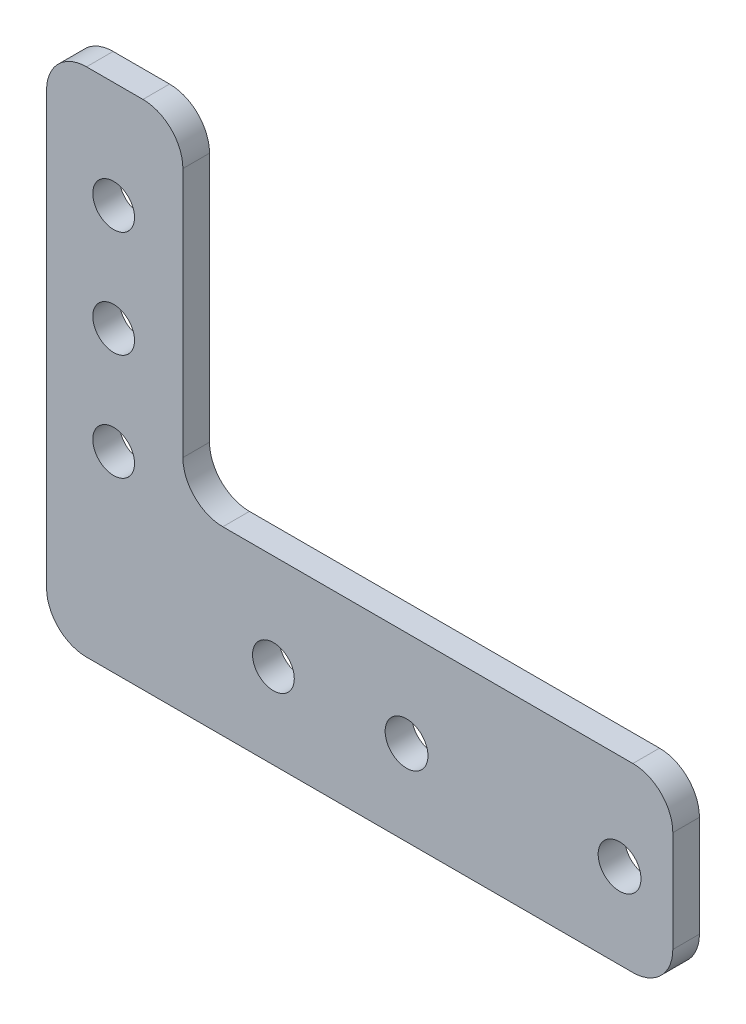
SolidWorks part; units mm, degrees
material "6061-T6 (SS)"
ref_plane "Front Plane" through (0, 0, 0) normal (0, 0, 1) x (1, 0, 0)
ref_plane "Top Plane" through (0, 0, 0) normal (0, 1, 0) x (1, 0, 0)
ref_plane "Right Plane" through (0, 0, 0) normal (1, 0, 0) x (0, 0, -1)
sketch "Sketch1" plane through (0, 0, 0) normal (0, 0, 1) x (1, 0, 0)
  line L1 (-41.275, -31.75) -> (41.275, -31.75)
  line L2 (-41.275, -31.75) -> (-41.275, 31.75)
  line L3 (-41.275, 31.75) -> (41.275, 31.75)
  line L4 (41.275, -31.75) -> (41.275, 31.75)
  line L5 (-41.275, -31.75) -> (41.275, 31.75) construction
  line L6 (-41.275, 31.75) -> (41.275, -31.75) construction
  line L7 (41.275, 31.75) -> (-17.145, 31.75)
  line L8 (41.275, 31.75) -> (41.275, -7.62)
  line L9 (41.275, -7.62) -> (-17.145, -7.62)
  line L10 (-17.145, 31.75) -> (-17.145, -7.62)
  line L11 (-41.275, -31.75) -> (-33.401, -31.75)
  line L12 (-41.275, -31.75) -> (-41.275, 31.75)
  line L13 (-41.275, 31.75) -> (-33.401, 31.75)
  line L14 (-33.401, -31.75) -> (-33.401, 31.75)
  line L15 (-33.401, -31.75) -> (41.275, -31.75)
  line L16 (-33.401, -31.75) -> (-33.401, -29.21)
  line L17 (-33.401, -29.21) -> (41.275, -29.21)
  line L18 (41.275, -31.75) -> (41.275, -29.21)
  circle A0 centre (-25.4, -19.05) radius 2.4892
  circle A1 centre (-25.4, -6.35) radius 2.4892
  circle A2 centre (-25.4, 6.35) radius 2.4892
  circle A3 centre (-25.4, 19.05) radius 2.4892
  circle A4 centre (-6.35, -19.05) radius 2.4892
  circle A5 centre (9.525, -19.05) radius 2.5527
  circle A7 centre (34.925, -19.05) radius 2.5527
  point P0 (0, 0)
  point P24 (0, 0)
  dimension "D7" = 4.9784
  dimension "D18" = 5.1054
  dimension "D1" = 82.55
  dimension "D2" = 63.5
  dimension "D3" = 24.13
  dimension "D4" = 24.13
  dimension "D5" = 7.874
  dimension "D6" = 63.5
  dimension "D8" = 15.875
  dimension "D9" = 12.7
  dimension "D10" = 12.7
  dimension "D11" = 12.7
  dimension "D12" = 12.7
  dimension "D13" = 25.4
  dimension "D14" = 27.051
  dimension "D15" = 15.875
  dimension "D16" = 2.54
extrude "Boss-Extrude1" add sketch "Sketch1" along normal blind 3.175 contours L14 L17 L4 L9 L10 L3 A5 A4 A3 A2 A1 A0 | A0 region at (-4.0851, -9.8474, 0) region at (-25.4, -19.05, 0)
fillet "Fillet1" radius 4.7625 6 edges at (-33.401, 31.75, 1.5875) (-17.145, 31.75, 1.5875) (-17.145, -7.62, 1.5875) (41.275, -7.62, 1.5875) (41.275, -29.21, 1.5875) (-33.401, -29.21, 1.5875)
